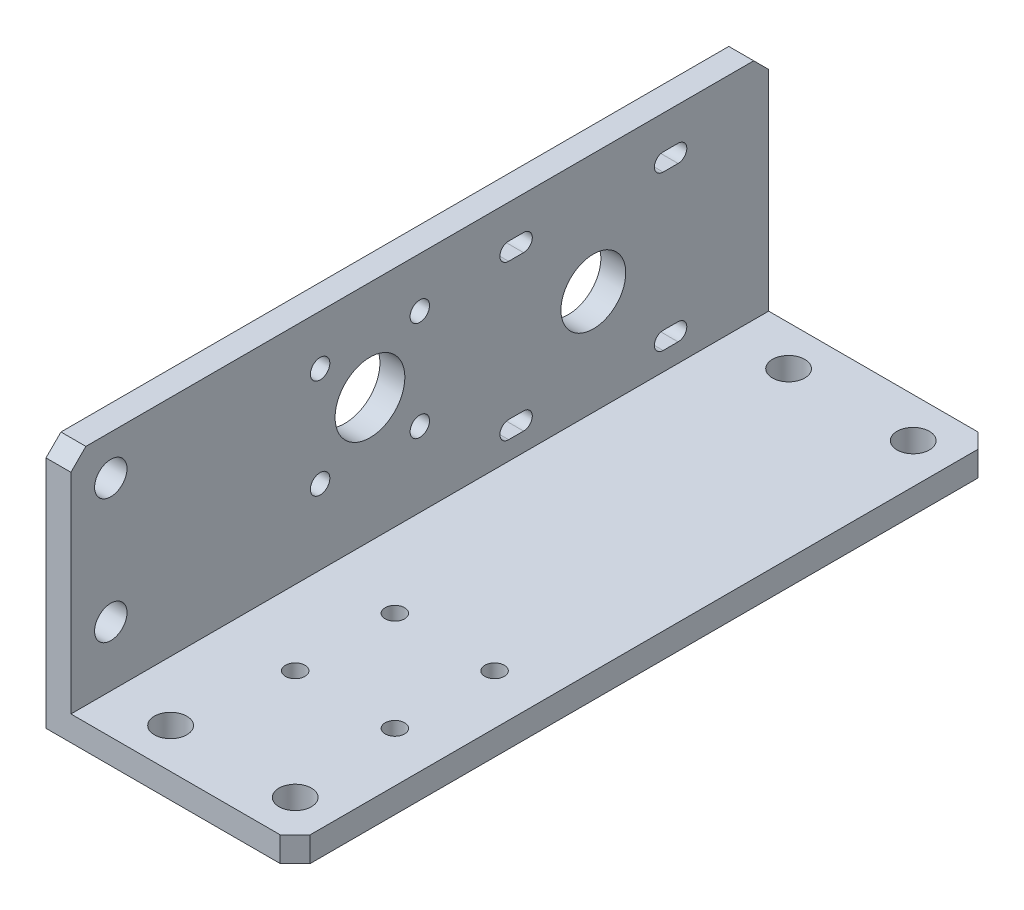
SolidWorks part; units mm, degrees
material "Lega 1060"
ref_plane "Piano frontale" through (0, 0, 0) normal (0, 0, 1) x (1, 0, 0)
ref_plane "Piano superiore" through (0, 0, 0) normal (0, 1, 0) x (1, 0, 0)
ref_plane "Piano destro" through (0, 0, 0) normal (1, 0, 0) x (0, 0, -1)
sketch "Schizzo1" plane through (0, 0, 0) normal (0, 0, 1) x (1, 0, 0)
  line L0 (0, 0) -> (0, 50)
  line L1 (0, 50) -> (5, 50)
  line L2 (5, 50) -> (5, 5)
  line L3 (5, 5) -> (50, 5)
  line L4 (50, 5) -> (50, 0)
  line L5 (50, 0) -> (0, 0)
  dimension "D1" = 5
  dimension "D2" = 5
  dimension "D3" = 50
  dimension "D4" = 50
extrude "Estrusione-Estrusione1" add sketch "Schizzo1" along normal blind 140
sketch "Schizzo2" plane through (0, 0, 0) normal (0, -1, 0) x (1, 0, 0)
  line L0 (5.4524, 132) -> (42.7933, 132) construction
  line L1 (0, 140) -> (50, 140) construction
  line L5 (50, 140) -> (50, 0) construction
  point P4 (17, 132)
  point P5 (42, 132)
  dimension "D1" = 8
  dimension "D2" = 25
  dimension "D3" = 8
sketch "Schizzo3" plane through (0, 0, 0) normal (-1, 0, 0) x (0, 0, 1)
  line L0 (132, 44.621) -> (132, 5.772) construction
  line L1 (140, 50) -> (140, 0) construction
  line L2 (140, 50) -> (0, 50) construction
  point P4 (132, 42)
  point P5 (132, 17)
  dimension "D1" = 8
  dimension "D2" = 8
  dimension "D3" = 25
hole_wizard "Foro Ø6.5 (6.5)-1" positions "Schizzo5" profile "Schizzo4" hole size "Ø6.5" standard "ISO" end condition through all
sketch "Schizzo5" plane through (0, 0, 0) normal (0, -1, 0) x (-1, 0, 0)
  point P0 (-17, -132)
  point P3 (-42, -132)
sketch "Schizzo4" plane through (17, 0, 132) normal (1, 0, 0) x (0, 0, -1)
  line L0 (0, 0) -> (0, 50)
  line L1 (0, 50) -> (3.25, 50)
  line L2 (3.25, 50) -> (3.25, 0)
  line L5 (3.25, 0) -> (0, 0)
  line L11 (0, -6.35) -> (0, 107.95) construction
  dimension "Thru Hole Dia." = 6.5
  dimension "Thru Hole Depth" = 50
hole_wizard "Foro Ø6.5 (6.5)-2" positions "Schizzo7" profile "Schizzo6" hole size "Ø6.5" standard "ISO"
sketch "Schizzo7" plane through (0, 0, 0) normal (-1, 0, 0) x (0, 0, 1)
  point P1 (132, 42)
  point P4 (132, 17)
sketch "Schizzo6" plane through (0, 42, 132) normal (0, 1, 0) x (0, 0, 1)
  line L0 (0, 0) -> (0, 6.9528)
  line L1 (0, 6.9528) -> (3.25, 5)
  line L2 (3.25, 5) -> (3.25, 0)
  line L5 (3.25, 0) -> (0, 0)
  line L10 (0, 6.9528) -> (-3.25, 5) construction
  line L11 (0, -6.35) -> (0, 107.95) construction
  dimension "Hole Dia." = 6.5
  dimension "Hole Depth" = 5
  dimension "Drill Angle" = 118
ref_plane "Piano1" through (0, 0, 70) normal (0, 0, 1) x (1, 0, 0)
mirror "Specchia1" about plane through (0, 0, 70) normal (0, 0, 1) of "Foro Ø6.5 (6.5)-1"
sketch "Schizzo10" plane through (0, 0, 0) normal (-1, 0, 0) x (0, 0, 1)
  line L3 (140, 50) -> (140, 0) construction
  line L5 (140, 50) -> (0, 50) construction
  circle A5 centre (80, 30) radius 7
  point P8 (80, 30)
  point P20 (80, 30)
  dimension "D7" = 14
  dimension "D5" = 60
  dimension "D6" = 20
extrude "Taglio-Estrusione3" cut sketch "Schizzo10" against normal up to next
sketch "Schizzo11" plane through (0, 0, 0) normal (0, -1, 0) x (1, 0, 0)
  line L0 (30, 100) -> (14.4837, 100) construction
  line L1 (30, 100) -> (4.5929, 74.5929) construction
  line L3 (50, 140) -> (50, 0) construction
  line L4 (0, 140) -> (50, 140) construction
  circle A0 centre (20, 90) radius 1.75
  circle A3 centre (20, 110) radius 1.75
  circle A4 centre (40, 110) radius 1.75
  circle A5 centre (40, 90) radius 1.75
  point P2 (30, 100)
  point P17 (30, 100)
  dimension "D2" = 3.5
  dimension "D1" = 20
  dimension "D3" = 45
  dimension "D5" = 20
  dimension "D6" = 40
  dimension "D4" = 4
sketch "Schizzo13" plane through (0, 0, 0) normal (-1, 0, 0) x (0, 0, 1)
  line L0 (68.5583, 26) -> (16.2744, 26) construction
  line L2 (140, 0) -> (0, 0) construction
  line L3 (18.1781, 41.5) -> (21.1781, 41.5) construction
  line L4 (18.1781, 43.25) -> (21.1781, 43.25)
  line L5 (18.1781, 39.75) -> (21.1781, 39.75)
  line L6 (18.1781, 10.5) -> (21.1781, 10.5) construction
  line L7 (18.1781, 8.75) -> (21.1781, 8.75)
  line L8 (18.1781, 12.25) -> (21.1781, 12.25)
  line L9 (35.1781, 26) -> (35.1781, 7.2619) construction
  line L10 (52.1781, 41.5) -> (49.1781, 41.5) construction
  line L11 (52.1781, 43.25) -> (49.1781, 43.25)
  line L12 (52.1781, 39.75) -> (49.1781, 39.75)
  line L13 (52.1781, 10.5) -> (49.1781, 10.5) construction
  line L14 (52.1781, 8.75) -> (49.1781, 8.75)
  line L15 (52.1781, 12.25) -> (49.1781, 12.25)
  arc A0 (52.1781, 43.25) -> (52.1781, 39.75) centre (52.1781, 41.5) cw
  arc A2 (18.1781, 43.25) -> (18.1781, 39.75) centre (18.1781, 41.5) ccw
  arc A3 (49.1781, 39.75) -> (49.1781, 43.25) centre (49.1781, 41.5) cw
  arc A4 (18.1781, 8.75) -> (18.1781, 12.25) centre (18.1781, 10.5) cw
  arc A5 (21.1781, 12.25) -> (21.1781, 8.75) centre (21.1781, 10.5) cw
  circle A6 centre (35.1781, 26) radius 6.5
  arc A7 (21.1781, 39.75) -> (21.1781, 43.25) centre (21.1781, 41.5) ccw
  circle A8 centre (80, 30) radius 7 construction
  arc A10 (52.1781, 8.75) -> (52.1781, 12.25) centre (52.1781, 10.5) ccw
  arc A11 (49.1781, 12.25) -> (49.1781, 8.75) centre (49.1781, 10.5) ccw
  point P8 (35.1781, 26)
  point P13 (50.6781, 41.5)
  point P17 (19.6781, 10.5)
  point P19 (35.1781, 26)
  point P22 (19.6781, 41.5)
  point P40 (50.6781, 10.5)
  dimension "D2" = 13
  dimension "D4" = 45
  dimension "D1" = 31
  dimension "D3" = 31
  dimension "D5" = 26
  dimension "D8" = 3.5
  dimension "D9" = 3
extrude "Taglio-Estrusione6" cut sketch "Schizzo13" against normal up to next
chamfer "Smusso1" distance 3 angle 45 4 edges at (50, 2.5, 0) (2.5, 50, 0) (50, 2.5, 140) (2.5, 50, 140)
sketch "Sketch1" plane through (0, 0, 0) normal (-1, 0, 0) x (0, 0, 1)
  line L0 (80, 30) -> (80, 46.7736) construction
  line L1 (80, 46.7736) -> (80, 30) construction
  line L2 (80, 30) -> (63.2264, 46.7736) construction
  line L3 (63.2264, 46.7736) -> (80, 30) construction
  line L4 (80, 30) -> (62.4784, 30) construction
  point P3 (70, 40)
  point P6 (90, 40)
  point P7 (70, 20)
  point P8 (90, 20)
  dimension "D1" = 45
  dimension "D2" = 10
hole_wizard "M3.5 Clearance Hole1" positions "3DSketch1" profile "Sketch2" hole size "M3.5" standard "ISO" end condition through all
sketch3d "3DSketch1"
  point P0 (0, 40, 70)
  point P3 (0, 40, 90)
  point P6 (0, 20, 90)
  point P9 (0, 20, 70)
sketch "Sketch2" plane through (0, 40, 70) normal (0, 1, 0) x (0, 0, 1)
  line L0 (0, 0) -> (0, 50)
  line L1 (0, 50) -> (1.95, 50)
  line L2 (1.95, 50) -> (1.95, 0)
  line L5 (1.95, 0) -> (0, 0)
  line L11 (0, -6.35) -> (0, 107.95) construction
  dimension "Thru Hole Dia." = 3.9
  dimension "Thru Hole Depth" = 50
hole_wizard "M3.5 Clearance Hole2" positions "3DSketch2" profile "Sketch3" hole size "M3.5" standard "ISO" end condition through all
sketch3d "3DSketch2"
  point P0 (20, 0, 110)
  point P3 (40, 0, 110)
  point P6 (40, 0, 90)
  point P9 (20, 0, 90)
sketch "Sketch3" plane through (20, 0, 110) normal (1, 0, 0) x (0, 0, -1)
  line L0 (0, 0) -> (0, 50)
  line L1 (0, 50) -> (1.95, 50)
  line L2 (1.95, 50) -> (1.95, 0)
  line L5 (1.95, 0) -> (0, 0)
  line L11 (0, -6.35) -> (0, 107.95) construction
  dimension "Thru Hole Dia." = 3.9
  dimension "Thru Hole Depth" = 50
sketch "Sketch4" plane through (0, 0, 0) normal (-1, 0, 0) x (0, 0, 1)
  line L0 (0, 47) -> (0, 0) construction
  line L1 (140, 0) -> (0, 0) construction
  point P0 (0, 5)
  dimension "D1" = 5
